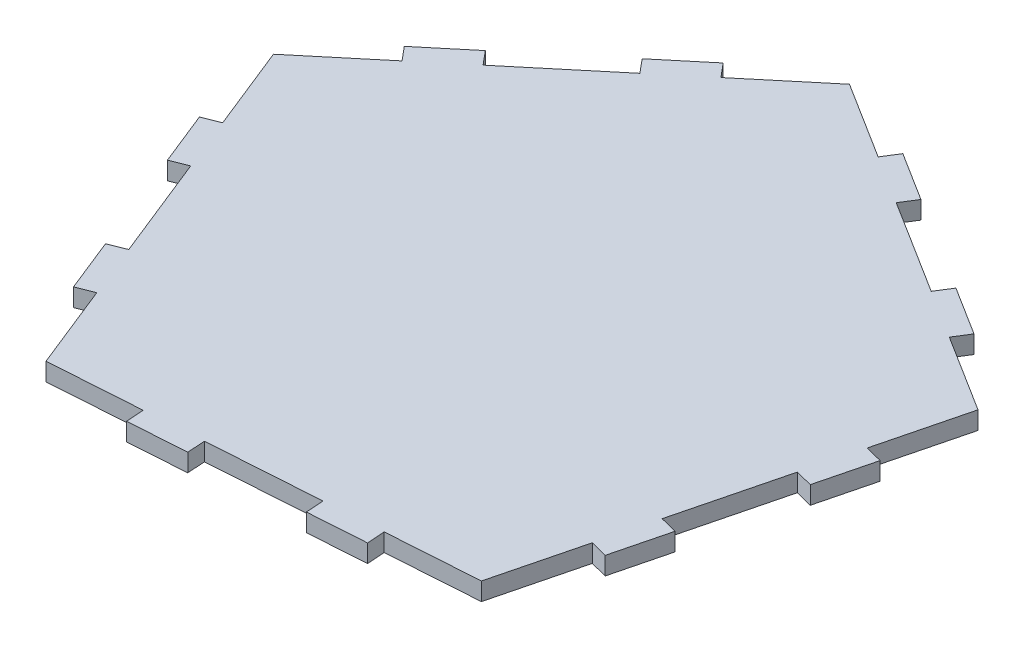
SolidWorks part; units mm, degrees
ref_plane "Front Plane" through (0, 0, 0) normal (0, 0, 1) x (1, 0, 0)
ref_plane "Top Plane" through (0, 0, 0) normal (0, 1, 0) x (1, 0, 0)
ref_plane "Right Plane" through (0, 0, 0) normal (1, 0, 0) x (0, 0, -1)
sketch "Sketch1" plane through (0, 0, 0) normal (0, 1, 0) x (1, 0, 0)
  line L1 (-63.7371, 16.0796) -> (-34.9884, -55.6487)
  line L2 (-34.9884, -55.6487) -> (42.1131, -50.4724)
  line L3 (42.1131, -50.4724) -> (61.0157, 24.4551)
  line L4 (61.0157, 24.4551) -> (-4.4033, 65.5865)
  line L5 (-4.4033, 65.5865) -> (-63.7371, 16.0796)
  circle A0 centre (0, 0) radius 53.18 construction
  dimension "D1" = 106.36
extrude "Boss-Extrude1" add sketch "Sketch1" along normal blind 3.18
sketch "Sketch2" plane through (0, 0, 0) normal (0, -1, 0) x (1, 0, 0)
  line L0 (-56.7625, 1.3223) -> (-53.8107, 0.1392)
  line L1 (-56.7625, 1.3223) -> (-53.124, 10.4003)
  line L2 (-53.8107, 0.1392) -> (-50.1723, 9.2172)
  line L3 (-53.124, 10.4003) -> (-50.1723, 9.2172)
  line L4 (-63.7371, -16.0796) -> (-34.9884, 55.6487) construction
  line L5 (-45.6015, 29.1689) -> (-41.9631, 38.2469)
  line L6 (-45.6015, 29.1689) -> (-42.6498, 27.9858)
  line L7 (-41.9631, 38.2469) -> (-39.0113, 37.0638)
  line L8 (-42.6498, 27.9858) -> (-39.0113, 37.0638)
  line L9 (-49.3628, 19.7846) -> (-19.2439, 7.7129) construction
  dimension "D1" = 3.18
  dimension "D2" = 9.78
  dimension "D3" = 10.11
extrude "Cut-Extrude1" [suppressed] cut sketch "Sketch2" against normal through all
ref_axis "Axis1" through (0, 3.339, 0) along (0, -1, 0)
pattern_circular "CirPattern1" [suppressed] count 5 over 360 about axis through (0, 3.339, 0) along (0, -1, 0) of bodies 102
sketch "Sketch3" plane through (0, 0, 0) normal (0, -1, 0) x (1, 0, 0)
  line L0 (-56.8443, 1.1181) -> (-53.8926, -0.065)
  line L1 (-56.8443, 1.1181) -> (-53.0421, 10.6045)
  line L2 (-53.8926, -0.065) -> (-50.0904, 9.4214)
  line L3 (-53.0421, 10.6045) -> (-50.0904, 9.4214)
  line L4 (-63.7371, -16.0796) -> (-34.9884, 55.6487) construction
  line L5 (-45.6834, 28.9647) -> (-42.7316, 27.7816)
  line L6 (-45.6834, 28.9647) -> (-41.8812, 38.4511)
  line L7 (-42.7316, 27.7816) -> (-38.9295, 37.268)
  line L8 (-41.8812, 38.4511) -> (-38.9295, 37.268)
  line L9 (0, 0) -> (-49.3628, 19.7846) construction
  line L10 (-65.563, -20.6353) -> (-62.6113, -21.8183)
  line L11 (-65.563, -20.6353) -> (-33.4497, 59.4878)
  line L12 (-62.6113, -21.8183) -> (-30.498, 58.3048)
  line L13 (-33.4497, 59.4878) -> (-30.498, 58.3048)
  line M14 (-63.7371, -16.0796) -> (-4.4033, -65.5865)
  line M17 (42.1131, 50.4724) -> (-34.9884, 55.6487)
  line M18 (-34.9884, 55.6487) -> (-63.7371, -16.0796)
  dimension "D1" = 10.22
  dimension "D3" = 3.18
  dimension "D4" = 3.18
  dimension "D2" = 9.89
extrude "Cut-Extrude2" cut sketch "Sketch3" against normal blind 10 contours L12 L0 M14 M18 | L12 L9 L11 L3 | L9 L12 L5 M18 | L8 L12 M17 M18 region at (-58.8985, 0, -8.3196) region at (-49.7266, 0, 14.603) region at (-46.0472, 0, 23.7831) region at (-36.8486, 0, 46.695)
pattern_circular "CirPattern2" count 5 over 360 about axis through (0, 3.339, 0) along (0, -1, 0) of "Cut-Extrude2"
equation "\"kerf\"= .22mm"
equation "\"tabWidth\"= 10 + \"kerf\" "
equation "\"tabSeperation\"= \"kerf\" / 2"
equation "\"tabThickness\"= 3.18"
equation "\"D1@Sketch2\"=\"tabThickness\""
equation "\"D3@Sketch3\"=\"tabThickness\""
equation "\"D4@Sketch3\"=\"tabThickness\""
equation "\"D3@Sketch2\"=10 +\"tabSeperation\""
equation "\"D2@Sketch3\"=10 -\"tabSeperation\""
equation "\"D1@Sketch3\"=10 +\"kerf\""
equation "\"tabLength\" = \"kerf\" + 12"
